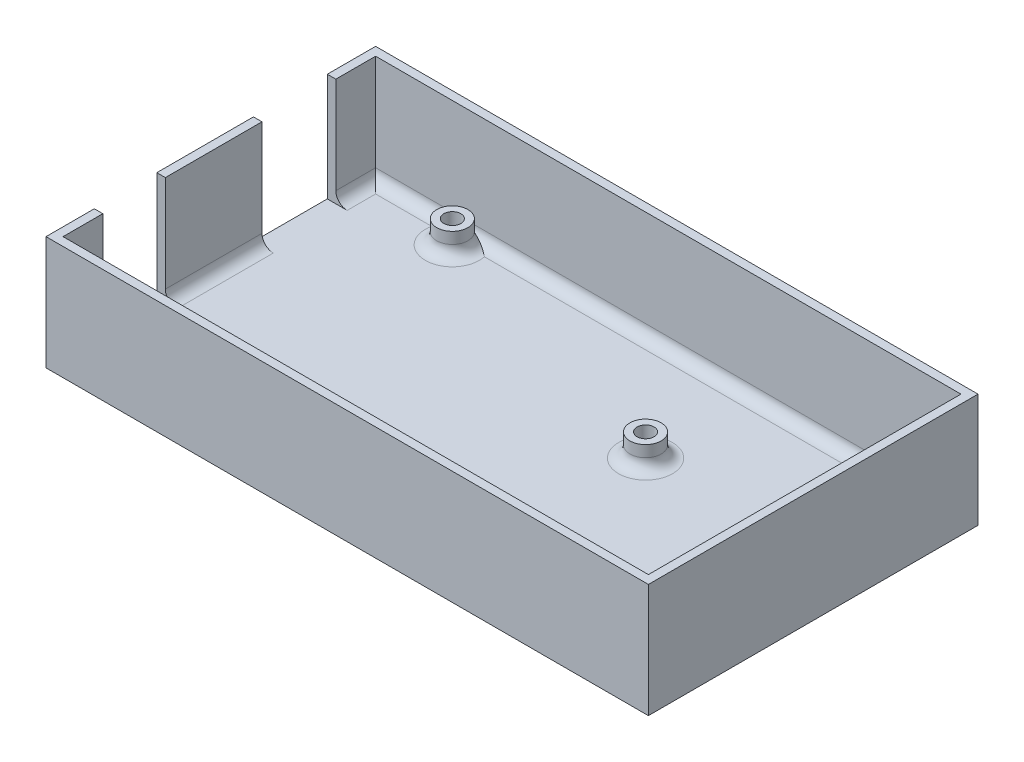
SolidWorks part; units mm, degrees
ref_plane "Front Plane" through (0, 0, 0) normal (0, 0, 1) x (1, 0, 0)
ref_plane "Top Plane" through (0, 0, 0) normal (0, 1, 0) x (1, 0, 0)
ref_plane "Right Plane" through (0, 0, 0) normal (1, 0, 0) x (0, 0, -1)
sketch "Sketch1" plane through (0, 0, 0) normal (0, 1, 0) x (1, 0, 0)
  line L0 (-51.5, 0) -> (51.5, 0) construction
  line L1 (-51.5, -27.5) -> (51.5, -27.5)
  line L2 (-51.5, -27.5) -> (-51.5, 27.5)
  line L3 (-51.5, 27.5) -> (51.5, 27.5)
  line L4 (51.5, -27.5) -> (51.5, 27.5)
  line L5 (0, 27.5) -> (0, -27.5) construction
  line L6 (-51.5, 24.5) -> (51.5, 24.5) construction
  line L7 (-35, 27.5) -> (-35, -27.5) construction
  line L8 (-51.5, -24) -> (51.5, -24) construction
  line L9 (-36.5, 27.5) -> (-36.5, -27.5) construction
  line L10 (14.5, -27.5) -> (14.5, 27.5) construction
  line L11 (-51.5, -19) -> (51.5, -19) construction
  line L12 (-51.5, 9) -> (51.5, 9) construction
  line L13 (46, 27.5) -> (46, -27.5) construction
  line L15 (-53, -29) -> (53, -29)
  line L16 (-53, -29) -> (-53, 29)
  line L17 (-53, 29) -> (53, 29)
  line L18 (53, -29) -> (53, 29)
  line L19 (-53, -29) -> (53, 29) construction
  line L20 (-53, 29) -> (53, -29) construction
  circle A0 centre (-35, 24.5) radius 1.5
  circle A2 centre (-36.5, -24) radius 1.5
  circle A3 centre (14.5, -19) radius 1.5
  circle A4 centre (14.5, 9) radius 1.5
  circle A5 centre (46, -24) radius 1.5
  point P0 (0, 0)
  point P14 (0, 0)
  point P37 (0, 0)
  dimension "D5" = 3.5
  dimension "D6" = 15
  dimension "D7" = 37
  dimension "D9" = 18.5
  dimension "D10" = 5.5
  dimension "D11" = 1.5
  dimension "D1" = 27.5
  dimension "D2" = 51.5
  dimension "D3" = 3
  dimension "D4" = 16.5
  dimension "D8" = 8.5
  dimension "D12" = 1.5
extrude "Boss-Extrude1" add sketch "Sketch1" along normal blind 1 contours L15 L18 L17 L16 L4 L1 L2 L3 | L1 L4 L3 L2 A5 A4 A3 A2 A0 region at (-0.0044, 0, -0.0421) region at (-51.7917, 0, 0)
sketch "Sketch4" plane through (0, 1, 0) normal (0, 1, 0) x (1, 0, 0)
  circle A0 centre (-36.5, -24) radius 1.5 construction
  circle A1 centre (14.5, -19) radius 1.5 construction
  circle A2 centre (46, -24) radius 1.5 construction
  circle A3 centre (14.5, 9) radius 1.5 construction
  circle A4 centre (-35, 24.5) radius 1.5 construction
  circle A5 centre (-36.5, -24) radius 1.5
  circle A6 centre (14.5, -19) radius 1.5
  circle A7 centre (46, -24) radius 1.5
  circle A8 centre (14.5, 9) radius 1.5
  circle A9 centre (-35, 24.5) radius 1.5
  circle A10 centre (-35, 24.5) radius 2.75
  circle A11 centre (14.5, 9) radius 2.75
  circle A12 centre (46, -24) radius 2.75
  circle A13 centre (14.5, -19) radius 2.75
  circle A14 centre (-36.5, -24) radius 2.75
  dimension "D1" = 5.5
  dimension "D2" = 5.5
  dimension "D3" = 5.5
  dimension "D4" = 5.5
  dimension "D5" = 5.5
extrude "Boss-Extrude4" add sketch "Sketch4" along normal blind 4
sketch "Sketch5" plane through (0, 1, 0) normal (0, 1, 0) x (1, 0, 0)
  line L0 (-51.5, 27.5) -> (-51.5, 20.5) construction
  line L1 (-51.5, -20.5) -> (-51.5, -27.5)
  line L2 (-51.5, -27.5) -> (-51.5, -20.5) construction
  line L4 (-51.5, -20.5) -> (-53, -20.5)
  line L5 (-51.5, -9.5) -> (-53, -9.5)
  line L6 (-51.5, 7.5) -> (-53, 7.5)
  line L7 (-51.5, 20.5) -> (-53, 20.5)
  line L8 (-51.5, -27.5) -> (51.5, -27.5)
  line L9 (51.5, -27.5) -> (51.5, 27.5)
  line L10 (51.5, 27.5) -> (-51.5, 27.5)
  line L11 (-51.5, 27.5) -> (-51.5, -27.5)
  line L12 (-51.5, -27.5) -> (51.5, -27.5)
  line L13 (51.5, -27.5) -> (51.5, 27.5)
  line L14 (51.5, 27.5) -> (-51.5, 27.5)
  line L15 (-51.5, 27.5) -> (-51.5, 20.5)
  line L16 (-53, -29) -> (53, -29)
  line L17 (53, -29) -> (53, 29)
  line L18 (53, 29) -> (-53, 29)
  line L19 (-53, 29) -> (-53, -29)
  line L20 (-53, -29) -> (53, -29)
  line L21 (53, -29) -> (53, 29)
  line L22 (53, 29) -> (-53, 29)
  line L23 (-53, 29) -> (-53, 20.5)
  line L24 (-53, 7.5) -> (-53, -9.5)
  line L25 (-51.5, 7.5) -> (-51.5, -9.5)
  line L26 (-53, -20.5) -> (-53, -29)
  dimension "D3" = 7
  dimension "D1" = 1.5
  dimension "D2" = 0
extrude "Boss-Extrude5" add sketch "Sketch5" along normal blind 19
fillet "Fillet1" radius 2 11 edges at (-51.5, 1, -24) (51.5, 1, 0) (46, 1, 26.75) (0, 1, 27.5) (-51.5, 1, 1) (-51.5, 1, 24) (-36.5, 1, 26.75) (14.5, 1, 21.75) (14.5, 1, -6.25) (-35, 1, -21.75) (0, 1, -27.5)
